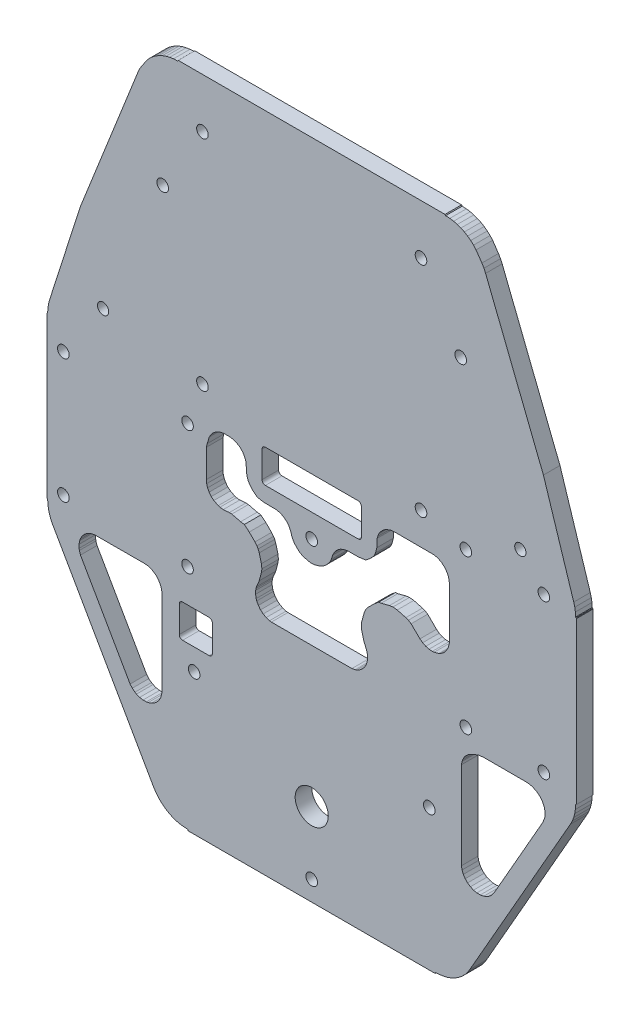
SolidWorks part; units mm, degrees
ref_plane "Plan de face" through (0, 0, 0) normal (1, 0, 0) x (0, 1, 0)
ref_plane "Plan de dessus" through (0, 0, 0) normal (0, 0, 1) x (0, 1, 0)
ref_plane "Plan de droite" through (0, 0, 0) normal (0, 1, 0) x (-1, 0, 0)
sketch "Esquisse1" plane through (0, 0, 0) normal (0, 0, 1) x (0, 1, 0)
  line L0 (0, 0) -> (-150.5414, 0) construction
  line L1 (-100, -80) -> (100, -80)
  line L2 (-100, -80) -> (-100, 80)
  line L3 (-100, 80) -> (100, 80)
  line L5 (-100, -80) -> (100, 80) construction
  line L6 (-100, 80) -> (100, -80) construction
  line L12 (-31, 38.8179) -> (-31, 42.3315) construction
  line L13 (-51, 40) -> (-41, 40)
  line L17 (-51, 40) -> (-51, 30)
  line L18 (-51, 30) -> (-41, 30)
  line L19 (-41, 40) -> (-41, 30)
  line L21 (-31.059, 37.5) -> (-30.571, 37.5) construction
  line L22 (-31, -46.5413) -> (-34.2714, -46.5413) construction
  line L28 (100, 80) -> (100, -80)
  line L30 (2, 15) -> (12, 15)
  line L31 (2, 15) -> (2, -15)
  line L32 (2, -15) -> (12, -15)
  line L33 (12, 15) -> (12, -15)
  circle A0 centre (-75, 0) radius 5
  circle A1 centre (-57.5, 35.5) radius 1.75
  circle A2 centre (-57.5, -35.5) radius 1.75
  circle A3 centre (65, 45) radius 1.75
  circle A4 centre (65, -45) radius 1.75
  circle A5 centre (-31, 37.5) radius 1.75
  circle A6 centre (-31, 75) radius 1.75
  circle A7 centre (6.5, 75) radius 1.75
  circle A8 centre (6.5, 37.5) radius 1.75
  circle A9 centre (-31, -46.5413) radius 1.75
  circle A10 centre (-31, -70.0913) radius 1.75
  circle A11 centre (15.5, -46.5413) radius 1.75
  circle A12 centre (15.5, -70.0913) radius 1.75
  circle A13 centre (-4.9993, 0) radius 1.75
  circle A16 centre (85, 33) radius 1.75
  circle A17 centre (85.0012, -33) radius 1.75
  circle A18 centre (19, 33) radius 1.75
  circle A19 centre (19.0012, -33) radius 1.75
  point P0 (0, 0)
  dimension "D3" = 10
  dimension "D9" = 3.5
  dimension "D10" = 35.5
  dimension "D11" = 17.5
  dimension "D5" = 3.5
  dimension "D6" = 45
  dimension "D7" = 15
  dimension "D16" = 37.5
  dimension "D17" = 37.5
  dimension "D18" = 37.5
  dimension "D19" = 3.5
  dimension "D20" = 3.5
  dimension "D21" = 3.5
  dimension "D22" = 3.5
  dimension "D23" = 10
  dimension "D24" = 5
  dimension "D25" = 3.5
  dimension "D26" = 3.5
  dimension "D27" = 3.5
  dimension "D28" = 3.5
  dimension "D29" = 46.5
  dimension "D30" = 46.5
  dimension "D31" = 23.55
  dimension "D32" = 23.55
  dimension "D35" = 3.5
  dimension "D36" = 3.5
  dimension "D41" = 66
  dimension "D42" = 66
  dimension "D47" = 3.5
  dimension "D48" = 3.5
  dimension "D50" = 66
  dimension "D52" = 33
  dimension "D33" = 14.9988
  dimension "D34" = 3.5
  dimension "D40" = 66
  dimension "D1" = 200
  dimension "D2" = 160
  dimension "D4" = 25
  dimension "D8" = 6.5
  dimension "D12" = 10
  dimension "D13" = 10
  dimension "D14" = 40
  dimension "D15" = 37.5
  dimension "D37" = 15
  dimension "D38" = 15
  dimension "D39" = 10
  dimension "D43" = 102
extrude "Boss.-Extru.1" add sketch "Esquisse1" along normal blind 5
fillet "Congé2" radius 1 8 edges at (-30, -51, 2.5) (-30, -41, 2.5) (-40, -41, 2.5) (-40, -51, 2.5) (15, 2, 2.5) (15, 12, 2.5) (-15, 12, 2.5) (-15, 2, 2.5)
sketch "Esquisse2" plane through (0, 0, 5) normal (0, 0, 1) x (1, 0, 0)
  line L0 (-110, 40) -> (0, 160)
  line L1 (0, 160) -> (110, 40)
  line L2 (110, 40) -> (110, -40)
  line L3 (110, -40) -> (0, -160)
  line L5 (0, -160) -> (-110, -40)
  line L6 (-110, -40) -> (-110, 40)
  line L14 (-573.5804, 598.1671) -> (-698.6982, -488.0825)
  line L15 (-80, 100) -> (-80, -100) construction
  line L16 (80, -100) -> (80, 100) construction
  line L17 (0, 70) -> (0, 33.5097) construction
  line L18 (-698.6982, -488.0825) -> (684.3, -647.3807)
  line L19 (0, 0) -> (-114.7759, 0) construction
  line L20 (684.3, -647.3807) -> (762.9047, 702.4319)
  line L21 (762.9047, 702.4319) -> (-573.5804, 598.1671)
  dimension "D1" = 160
  dimension "D2" = 160
  dimension "D3" = 40
  dimension "D4" = 40
  dimension "D5" = 40
  dimension "D6" = 40
  dimension "D7" = 110
extrude "Enlèv. mat.-Extru.1" cut sketch "Esquisse2" against normal through all
sketch "Esquisse3" plane through (0, 0, 0) normal (0, 0, 1) x (0, 1, 0)
  circle A0 centre (-94.0015, 0.004) radius 1.75
extrude "Trou cuve direction" cut sketch "Esquisse3" along normal through all
sketch "Esquisse4" plane through (0, 0, 5) normal (0, 0, 1) x (1, 0, 0)
  line L0 (-82.024, 47.0385) -> (-45.024, 103.0385)
  line L1 (-45.024, 103.0385) -> (-83.024, 103.0385)
  line L2 (-83.024, 103.0385) -> (-83.024, 47.0385)
  line L3 (-83.024, 47.0385) -> (-82.024, 47.0385)
  line L4 (82.016, 47.0385) -> (45.016, 103.0385)
  line L5 (45.016, 103.0385) -> (83.016, 103.0385)
  line L6 (83.016, 103.0385) -> (83.016, 47.0385)
  line L7 (83.016, 47.0385) -> (82.016, 47.0385)
  circle A0 centre (-63.004, 23.7385) radius 1.7
  circle A2 centre (62.996, 23.7385) radius 1.7
extrude "Pointe avant, trous berceau et cables" cut sketch "Esquisse4" against normal through all
sketch "Esquisse5" plane through (0, 0, 5) normal (0, 0, 1) x (1, 0, 0)
  line L0 (-80.324, 14.3635) -> (-80.254, 14.1705)
  line L1 (-80.254, 14.1705) -> (-80.076, 14.0675)
  line L2 (-80.076, 14.0675) -> (-79.874, 14.1035)
  line L3 (-79.874, 14.1035) -> (-79.742, 14.2605)
  line L4 (-79.742, 14.2605) -> (-79.662, 15.5635)
  line L5 (-79.662, 15.5635) -> (-79.477, 16.7515)
  line L6 (-79.477, 16.7515) -> (-79.17, 17.9215)
  line L7 (-79.17, 17.9215) -> (-69.975, 46.6925)
  line L8 (-69.975, 46.6925) -> (-52.443, 90.8885)
  line L9 (-52.443, 90.8885) -> (-51.938, 91.9925)
  line L10 (-51.938, 91.9925) -> (-51.322, 93.0375)
  line L11 (-51.322, 93.0375) -> (-49.68, 95.4185)
  line L12 (-49.68, 95.4185) -> (-48.909, 96.2775)
  line L13 (-48.909, 96.2775) -> (-48.056, 97.0555)
  line L14 (-48.056, 97.0555) -> (-47.132, 97.7465)
  line L15 (-47.132, 97.7465) -> (-46.143, 98.3425)
  line L16 (-46.143, 98.3425) -> (-45.101, 98.8385)
  line L17 (-45.101, 98.8385) -> (-44.015, 99.2295)
  line L18 (-44.015, 99.2295) -> (-42.896, 99.5105)
  line L19 (-42.896, 99.5105) -> (-41.754, 99.6815)
  line L20 (-41.754, 99.6815) -> (-40.499, 99.7565)
  line L21 (-40.499, 99.7565) -> (-40.358, 99.8635)
  line L22 (-40.358, 99.8635) -> (-40.302, 100.0305)
  line L23 (-40.302, 100.0305) -> (-40.349, 100.2015)
  line L24 (-40.349, 100.2015) -> (-40.485, 100.3145)
  line L25 (-40.485, 100.3145) -> (-47.056, 100.3385)
  line L26 (-47.056, 100.3385) -> (-47.288, 100.2275)
  line L27 (-47.288, 100.2275) -> (-80.302, 50.2545)
  line L28 (-80.302, 50.2545) -> (-80.324, 14.3635)
  line L29 (-80.324, -72.6885) -> (-80.245, -72.8915)
  line L30 (-80.245, -72.8915) -> (-55.173, -100.2225)
  line L31 (-55.173, -100.2225) -> (-37.575, -100.2615)
  line L32 (-37.575, -100.2615) -> (-37.328, -100.1315)
  line L33 (-37.328, -100.1315) -> (-37.286, -99.8825)
  line L34 (-37.286, -99.8825) -> (-37.476, -99.6785)
  line L35 (-37.476, -99.6785) -> (-39.799, -99.4475)
  line L36 (-39.799, -99.4475) -> (-40.886, -99.1825)
  line L37 (-40.886, -99.1825) -> (-41.942, -98.8155)
  line L38 (-41.942, -98.8155) -> (-42.959, -98.3485)
  line L39 (-42.959, -98.3485) -> (-43.926, -97.7875)
  line L40 (-43.926, -97.7875) -> (-44.835, -97.1365)
  line L41 (-44.835, -97.1365) -> (-45.678, -96.4015)
  line L42 (-45.678, -96.4015) -> (-46.447, -95.5885)
  line L43 (-46.447, -95.5885) -> (-47.135, -94.7065)
  line L44 (-47.135, -94.7065) -> (-47.739, -93.7575)
  line L45 (-47.739, -93.7575) -> (-78.18, -40.4485)
  line L46 (-78.18, -40.4485) -> (-78.73, -39.3585)
  line L47 (-78.73, -39.3585) -> (-79.161, -38.2235)
  line L48 (-79.161, -38.2235) -> (-79.473, -37.0505)
  line L49 (-79.473, -37.0505) -> (-79.661, -35.8525)
  line L50 (-79.661, -35.8525) -> (-79.733, -34.5655)
  line L51 (-79.733, -34.5655) -> (-79.849, -34.3965)
  line L52 (-79.849, -34.3965) -> (-80.017, -34.3405)
  line L53 (-80.017, -34.3405) -> (-80.234, -34.4255)
  line L54 (-80.234, -34.4255) -> (-80.324, -34.6405)
  line L55 (-80.324, -34.6405) -> (-80.324, -72.6885)
  line L56 (54.976, -100.2615) -> (55.197, -100.1645)
  line L57 (55.197, -100.1645) -> (80.256, -72.7975)
  line L58 (80.256, -72.7975) -> (80.276, -34.7105)
  line L59 (80.276, -34.7105) -> (80.224, -34.5415)
  line L60 (80.224, -34.5415) -> (80.086, -34.4305)
  line L61 (80.086, -34.4305) -> (79.853, -34.4365)
  line L62 (79.853, -34.4365) -> (79.694, -34.6075)
  line L63 (79.694, -34.6075) -> (79.613, -35.9225)
  line L64 (79.613, -35.9225) -> (79.425, -37.1205)
  line L65 (79.425, -37.1205) -> (79.113, -38.2935)
  line L66 (79.113, -38.2935) -> (78.682, -39.4285)
  line L67 (78.682, -39.4285) -> (78.132, -40.5185)
  line L68 (78.132, -40.5185) -> (47.731, -93.7575)
  line L69 (47.731, -93.7575) -> (47.127, -94.7065)
  line L70 (47.127, -94.7065) -> (46.439, -95.5885)
  line L71 (46.439, -95.5885) -> (45.67, -96.4015)
  line L72 (45.67, -96.4015) -> (44.827, -97.1365)
  line L73 (44.827, -97.1365) -> (43.918, -97.7875)
  line L74 (43.918, -97.7875) -> (42.951, -98.3485)
  line L75 (42.951, -98.3485) -> (41.934, -98.8155)
  line L76 (41.934, -98.8155) -> (40.878, -99.1825)
  line L77 (40.878, -99.1825) -> (39.791, -99.4475)
  line L78 (39.791, -99.4475) -> (38.685, -99.6075)
  line L79 (38.685, -99.6075) -> (37.496, -99.6705)
  line L80 (37.496, -99.6705) -> (37.329, -99.7795)
  line L81 (37.329, -99.7795) -> (37.267, -99.9685)
  line L82 (37.267, -99.9685) -> (37.358, -100.1765)
  line L83 (37.358, -100.1765) -> (37.567, -100.2615)
  line L84 (37.567, -100.2615) -> (54.976, -100.2615)
  line L85 (80.276, 50.1285) -> (47.232, 100.2275)
  line L86 (47.232, 100.2275) -> (47, 100.3385)
  line L87 (47, 100.3385) -> (40.545, 100.3385)
  line L88 (40.545, 100.3385) -> (40.353, 100.2685)
  line L89 (40.353, 100.2685) -> (40.248, 100.0015)
  line L90 (40.248, 100.0015) -> (40.443, 99.7565)
  line L91 (40.443, 99.7565) -> (41.698, 99.6815)
  line L92 (41.698, 99.6815) -> (42.84, 99.5105)
  line L93 (42.84, 99.5105) -> (43.959, 99.2295)
  line L94 (43.959, 99.2295) -> (45.045, 98.8385)
  line L95 (45.045, 98.8385) -> (46.087, 98.3425)
  line L96 (46.087, 98.3425) -> (47.076, 97.7465)
  line L97 (47.076, 97.7465) -> (48, 97.0555)
  line L98 (48, 97.0555) -> (48.852, 96.2775)
  line L99 (48.852, 96.2775) -> (49.624, 95.4185)
  line L100 (49.624, 95.4185) -> (51.386, 92.8555)
  line L101 (51.386, 92.8555) -> (52.002, 91.8095)
  line L102 (52.002, 91.8095) -> (52.507, 90.7065)
  line L103 (52.507, 90.7065) -> (69.967, 46.6925)
  line L104 (69.967, 46.6925) -> (79.122, 18.0475)
  line L105 (79.122, 18.0475) -> (79.429, 16.8775)
  line L106 (79.429, 16.8775) -> (79.614, 15.6895)
  line L107 (79.614, 15.6895) -> (79.685, 14.4145)
  line L108 (79.685, 14.4145) -> (79.801, 14.2445)
  line L109 (79.801, 14.2445) -> (79.969, 14.1885)
  line L110 (79.969, 14.1885) -> (80.186, 14.2735)
  line L111 (80.186, 14.2735) -> (80.276, 14.4885)
  line L112 (80.276, 14.4885) -> (80.276, 50.1285)
  line L113 (-12.185, -32.8365) -> (12.119, -32.8335)
  line L114 (12.119, -32.8335) -> (13.124, -32.6305)
  line L115 (13.124, -32.6305) -> (13.649, -32.4395)
  line L116 (13.649, -32.4395) -> (14.549, -31.9485)
  line L117 (14.549, -31.9485) -> (14.994, -31.6115)
  line L118 (14.994, -31.6115) -> (15.71, -30.8775)
  line L119 (15.71, -30.8775) -> (16.036, -30.4245)
  line L120 (16.036, -30.4245) -> (16.504, -29.5115)
  line L121 (16.504, -29.5115) -> (16.798, -28.4675)
  line L122 (16.798, -28.4675) -> (16.875, -27.4445)
  line L123 (16.875, -27.4445) -> (16.833, -26.8875)
  line L124 (16.833, -26.8875) -> (16.595, -25.8595)
  line L125 (16.595, -25.8595) -> (15.799, -23.9905)
  line L126 (15.799, -23.9905) -> (15.101, -21.3865)
  line L127 (15.101, -21.3865) -> (14.959, -20.3455)
  line L128 (14.959, -20.3455) -> (15.036, -19.3675)
  line L129 (15.036, -19.3675) -> (15.896, -16.1555)
  line L130 (15.896, -16.1555) -> (16.453, -15.0635)
  line L131 (16.453, -15.0635) -> (17.047, -14.3505)
  line L132 (17.047, -14.3505) -> (18.779, -12.6185)
  line L133 (18.779, -12.6185) -> (20.268, -11.3815)
  line L134 (20.268, -11.3815) -> (20.983, -11.3155)
  line L135 (20.983, -11.3155) -> (23.488, -10.6725)
  line L136 (23.488, -10.6725) -> (24.529, -10.5295)
  line L137 (24.529, -10.5295) -> (25.816, -10.6725)
  line L138 (25.816, -10.6725) -> (28.419, -11.3705)
  line L139 (28.419, -11.3705) -> (29.173, -11.6555)
  line L140 (29.173, -11.6555) -> (30.01, -12.1685)
  line L141 (30.01, -12.1685) -> (32.687, -14.7885)
  line L142 (32.687, -14.7885) -> (33.499, -15.4035)
  line L143 (33.499, -15.4035) -> (34.442, -15.8615)
  line L144 (34.442, -15.8615) -> (35.428, -16.1205)
  line L145 (35.428, -16.1205) -> (36.417, -16.1865)
  line L146 (36.417, -16.1865) -> (36.955, -16.1455)
  line L147 (36.955, -16.1455) -> (38.398, -15.7455)
  line L148 (38.398, -15.7455) -> (38.881, -15.5045)
  line L149 (38.881, -15.5045) -> (39.694, -14.9395)
  line L150 (39.694, -14.9395) -> (40.088, -14.5705)
  line L151 (40.088, -14.5705) -> (40.707, -13.7965)
  line L152 (40.707, -13.7965) -> (41.192, -12.8675)
  line L153 (41.192, -12.8675) -> (41.475, -11.9185)
  line L154 (41.475, -11.9185) -> (41.552, -11.3845)
  line L155 (41.552, -11.3845) -> (41.576, 4.0535)
  line L156 (41.576, 4.0535) -> (41.471, 5.0865)
  line L157 (41.471, 5.0865) -> (41.167, 6.0805)
  line L158 (41.167, 6.0805) -> (40.674, 6.9955)
  line L159 (40.674, 6.9955) -> (40.013, 7.7965)
  line L160 (40.013, 7.7965) -> (39.208, 8.4535)
  line L161 (39.208, 8.4535) -> (38.318, 8.9295)
  line L162 (38.318, 8.9295) -> (37.324, 9.2335)
  line L163 (37.324, 9.2335) -> (36.781, 9.3145)
  line L164 (36.781, 9.3145) -> (24.961, 9.3385)
  line L165 (24.961, 9.3385) -> (23.928, 9.2335)
  line L166 (23.928, 9.2335) -> (22.491, 8.7195)
  line L167 (22.491, 8.7195) -> (22.019, 8.4365)
  line L168 (22.019, 8.4365) -> (21.218, 7.7755)
  line L169 (21.218, 7.7755) -> (20.578, 6.9955)
  line L170 (20.578, 6.9955) -> (20.295, 6.5235)
  line L171 (20.295, 6.5235) -> (19.909, 5.5905)
  line L172 (19.909, 5.5905) -> (19.775, 5.0575)
  line L173 (19.775, 5.0575) -> (19.644, 2.5275)
  line L174 (19.644, 2.5275) -> (19.267, 0.9715)
  line L175 (19.267, 0.9715) -> (18.968, 0.2985)
  line L176 (18.968, 0.2985) -> (18.567, -0.3195)
  line L177 (18.567, -0.3195) -> (17.525, -1.3975)
  line L178 (17.525, -1.3975) -> (16.364, -2.3355)
  line L179 (16.364, -2.3355) -> (14.283, -2.6475)
  line L180 (14.283, -2.6475) -> (10.727, -2.6905)
  line L181 (10.727, -2.6905) -> (9.684, -2.9065)
  line L182 (9.684, -2.9065) -> (8.705, -3.3265)
  line L183 (8.705, -3.3265) -> (7.83, -3.9345)
  line L184 (7.83, -3.9345) -> (7.112, -4.6815)
  line L185 (7.112, -4.6815) -> (6.804, -5.1165)
  line L186 (6.804, -5.1165) -> (6.325, -6.0685)
  line L187 (6.325, -6.0685) -> (5.917, -7.4025)
  line L188 (5.917, -7.4025) -> (5.617, -8.0755)
  line L189 (5.617, -8.0755) -> (5.061, -8.8845)
  line L190 (5.061, -8.8845) -> (4.134, -9.8355)
  line L191 (4.134, -9.8355) -> (3.304, -10.4795)
  line L192 (3.304, -10.4795) -> (2.418, -10.9015)
  line L193 (2.418, -10.9015) -> (0.832, -11.3265)
  line L194 (0.832, -11.3265) -> (-0.147, -11.4035)
  line L195 (-0.147, -11.4035) -> (-1.188, -11.2615)
  line L196 (-1.188, -11.2615) -> (-2.696, -10.8135)
  line L197 (-2.696, -10.8135) -> (-3.558, -10.3455)
  line L198 (-3.558, -10.3455) -> (-4.182, -9.8355)
  line L199 (-4.182, -9.8355) -> (-5.109, -8.8845)
  line L200 (-5.109, -8.8845) -> (-5.665, -8.0755)
  line L201 (-5.665, -8.0755) -> (-5.965, -7.4025)
  line L202 (-5.965, -7.4025) -> (-6.373, -6.0685)
  line L203 (-6.373, -6.0685) -> (-6.852, -5.1165)
  line L204 (-6.852, -5.1165) -> (-7.49, -4.3015)
  line L205 (-7.49, -4.3015) -> (-7.878, -3.9345)
  line L206 (-7.878, -3.9345) -> (-8.753, -3.3265)
  line L207 (-8.753, -3.3265) -> (-9.732, -2.9065)
  line L208 (-9.732, -2.9065) -> (-10.775, -2.6905)
  line L209 (-10.775, -2.6905) -> (-14.331, -2.6475)
  line L210 (-14.331, -2.6475) -> (-16.415, -2.3185)
  line L211 (-16.415, -2.3185) -> (-17.807, -1.1865)
  line L212 (-17.807, -1.1865) -> (-18.759, -0.1205)
  line L213 (-18.759, -0.1205) -> (-19.127, 0.5175)
  line L214 (-19.127, 0.5175) -> (-19.413, 1.2715)
  line L215 (-19.413, 1.2715) -> (-19.692, 2.5275)
  line L216 (-19.692, 2.5275) -> (-19.823, 5.0575)
  line L217 (-19.823, 5.0575) -> (-20.133, 6.0805)
  line L218 (-20.133, 6.0805) -> (-20.609, 6.9705)
  line L219 (-20.609, 6.9705) -> (-20.937, 7.4115)
  line L220 (-20.937, 7.4115) -> (-21.651, 8.1255)
  line L221 (-21.651, 8.1255) -> (-22.092, 8.4535)
  line L222 (-22.092, 8.4535) -> (-23.01, 8.9405)
  line L223 (-23.01, 8.9405) -> (-24.005, 9.2395)
  line L224 (-24.005, 9.2395) -> (-25.009, 9.3385)
  line L225 (-25.009, 9.3385) -> (-26.584, 9.3155)
  line L226 (-26.584, 9.3155) -> (-27.576, 9.1265)
  line L227 (-27.576, 9.1265) -> (-28.08, 8.9515)
  line L228 (-28.08, 8.9515) -> (-28.975, 8.4865)
  line L229 (-28.975, 8.4865) -> (-29.766, 7.8595)
  line L230 (-29.766, 7.8595) -> (-30.424, 7.0935)
  line L231 (-30.424, 7.0935) -> (-30.925, 6.2175)
  line L232 (-30.925, 6.2175) -> (-31.569, 4.1375)
  line L233 (-31.569, 4.1375) -> (-31.793, 3.0845)
  line L234 (-31.793, 3.0845) -> (-31.824, -5.4005)
  line L235 (-31.824, -5.4005) -> (-31.724, -6.4115)
  line L236 (-31.724, -6.4115) -> (-31.443, -7.3585)
  line L237 (-31.443, -7.3585) -> (-30.977, -8.2605)
  line L238 (-30.977, -8.2605) -> (-30.326, -9.0785)
  line L239 (-30.326, -9.0785) -> (-29.552, -9.7365)
  line L240 (-29.552, -9.7365) -> (-28.219, -10.4075)
  line L241 (-28.219, -10.4075) -> (-27.702, -10.5535)
  line L242 (-27.702, -10.5535) -> (-26.723, -10.6825)
  line L243 (-26.723, -10.6825) -> (-24.871, -10.5295)
  line L244 (-24.871, -10.5295) -> (-24.135, -10.5685)
  line L245 (-24.135, -10.5685) -> (-21.474, -11.2345)
  line L246 (-21.474, -11.2345) -> (-20.357, -11.4015)
  line L247 (-20.357, -11.4015) -> (-18.876, -12.6185)
  line L248 (-18.876, -12.6185) -> (-17.144, -14.3505)
  line L249 (-17.144, -14.3505) -> (-16.549, -15.0635)
  line L250 (-16.549, -15.0635) -> (-16.18, -15.7015)
  line L251 (-16.18, -15.7015) -> (-15.86, -16.5735)
  line L252 (-15.86, -16.5735) -> (-15.197, -19.0595)
  line L253 (-15.197, -19.0595) -> (-15.055, -20.3455)
  line L254 (-15.055, -20.3455) -> (-15.197, -21.3865)
  line L255 (-15.197, -21.3865) -> (-15.86, -23.8725)
  line L256 (-15.86, -23.8725) -> (-16.691, -25.8595)
  line L257 (-16.691, -25.8595) -> (-16.836, -26.3675)
  line L258 (-16.836, -26.3675) -> (-16.933, -26.9175)
  line L259 (-16.933, -26.9175) -> (-16.958, -27.9425)
  line L260 (-16.958, -27.9425) -> (-16.778, -28.9825)
  line L261 (-16.778, -28.9825) -> (-16.6, -29.5115)
  line L262 (-16.6, -29.5115) -> (-16.116, -30.4495)
  line L263 (-16.116, -30.4495) -> (-15.456, -31.2725)
  line L264 (-15.456, -31.2725) -> (-14.645, -31.9485)
  line L265 (-14.645, -31.9485) -> (-13.745, -32.4395)
  line L266 (-13.745, -32.4395) -> (-12.737, -32.7535)
  line L267 (-12.737, -32.7535) -> (-12.185, -32.8365)
  line L268 (48.838, -36.9415) -> (47.477, -37.6125)
  line L269 (47.477, -37.6125) -> (47.047, -37.9415)
  line L270 (47.047, -37.9415) -> (46.353, -38.6525)
  line L271 (46.353, -38.6525) -> (46.035, -39.0905)
  line L272 (46.035, -39.0905) -> (45.573, -39.9705)
  line L273 (45.573, -39.9705) -> (45.393, -40.4805)
  line L274 (45.393, -40.4805) -> (45.202, -41.4565)
  line L275 (45.202, -41.4565) -> (45.2, -67.8725)
  line L276 (45.2, -67.8725) -> (45.396, -68.8815)
  line L277 (45.396, -68.8815) -> (45.782, -69.8335)
  line L278 (45.782, -69.8335) -> (46.346, -70.6935)
  line L279 (46.346, -70.6935) -> (47.065, -71.4285)
  line L280 (47.065, -71.4285) -> (47.912, -72.0105)
  line L281 (47.912, -72.0105) -> (48.856, -72.4185)
  line L282 (48.856, -72.4185) -> (49.86, -72.6365)
  line L283 (49.86, -72.6365) -> (50.888, -72.6565)
  line L284 (50.888, -72.6565) -> (51.928, -72.4695)
  line L285 (51.928, -72.4695) -> (53.307, -71.8525)
  line L286 (53.307, -71.8525) -> (54.14, -71.2025)
  line L287 (54.14, -71.2025) -> (55.071, -70.0135)
  line L288 (55.071, -70.0135) -> (69.787, -44.2435)
  line L289 (69.787, -44.2435) -> (70.341, -42.8195)
  line L290 (70.341, -42.8195) -> (70.437, -42.2785)
  line L291 (70.437, -42.2785) -> (70.464, -41.2675)
  line L292 (70.464, -41.2675) -> (70.292, -40.2425)
  line L293 (70.292, -40.2425) -> (70.121, -39.7195)
  line L294 (70.121, -39.7195) -> (69.653, -38.7905)
  line L295 (69.653, -38.7905) -> (69.033, -37.9925)
  line L296 (69.033, -37.9925) -> (68.635, -37.6125)
  line L297 (68.635, -37.6125) -> (67.784, -37.0145)
  line L298 (67.784, -37.0145) -> (66.751, -36.5285)
  line L299 (66.751, -36.5285) -> (65.82, -36.2585)
  line L300 (65.82, -36.2585) -> (64.814, -36.1615)
  line L301 (64.814, -36.1615) -> (51.757, -36.1615)
  line L302 (51.757, -36.1615) -> (50.306, -36.3685)
  line L303 (50.306, -36.3685) -> (48.838, -36.9415)
  line L304 (-50.524, -36.6615) -> (-65.536, -36.6895)
  line L305 (-65.536, -36.6895) -> (-66.539, -36.8915)
  line L306 (-66.539, -36.8915) -> (-67.537, -37.3115)
  line L307 (-67.537, -37.3115) -> (-68.383, -37.8865)
  line L308 (-68.383, -37.8865) -> (-68.771, -38.2435)
  line L309 (-68.771, -38.2435) -> (-69.448, -39.0885)
  line L310 (-69.448, -39.0885) -> (-69.917, -39.9985)
  line L311 (-69.917, -39.9985) -> (-70.088, -40.4965)
  line L312 (-70.088, -40.4965) -> (-70.279, -41.5625)
  line L313 (-70.279, -41.5625) -> (-70.258, -42.5855)
  line L314 (-70.258, -42.5855) -> (-70.17, -43.1055)
  line L315 (-70.17, -43.1055) -> (-69.829, -44.1325)
  line L316 (-69.829, -44.1325) -> (-54.841, -70.3765)
  line L317 (-54.841, -70.3765) -> (-54.188, -71.1315)
  line L318 (-54.188, -71.1315) -> (-53.379, -71.7675)
  line L319 (-53.379, -71.7675) -> (-52.907, -72.0365)
  line L320 (-52.907, -72.0365) -> (-51.948, -72.4075)
  line L321 (-51.948, -72.4075) -> (-50.936, -72.5865)
  line L322 (-50.936, -72.5865) -> (-49.937, -72.5695)
  line L323 (-49.937, -72.5695) -> (-49.401, -72.4815)
  line L324 (-49.401, -72.4815) -> (-48.422, -72.1675)
  line L325 (-48.422, -72.1675) -> (-47.135, -71.3775)
  line L326 (-47.135, -71.3775) -> (-46.735, -71.0085)
  line L327 (-46.735, -71.0085) -> (-46.107, -70.2315)
  line L328 (-46.107, -70.2315) -> (-45.614, -69.2965)
  line L329 (-45.614, -69.2965) -> (-45.327, -68.3405)
  line L330 (-45.327, -68.3405) -> (-45.248, -67.8025)
  line L331 (-45.248, -67.8025) -> (-45.224, -41.9615)
  line L332 (-45.224, -41.9615) -> (-45.329, -40.9135)
  line L333 (-45.329, -40.9135) -> (-45.633, -39.9195)
  line L334 (-45.633, -39.9195) -> (-46.418, -38.6105)
  line L335 (-46.418, -38.6105) -> (-47.173, -37.8555)
  line L336 (-47.173, -37.8555) -> (-48.482, -37.0705)
  line L337 (-48.482, -37.0705) -> (-49.505, -36.7605)
  line L338 (-49.505, -36.7605) -> (-50.524, -36.6615)
extrude "Forme arrondie et allegement" cut sketch "Esquisse5" against normal through all
